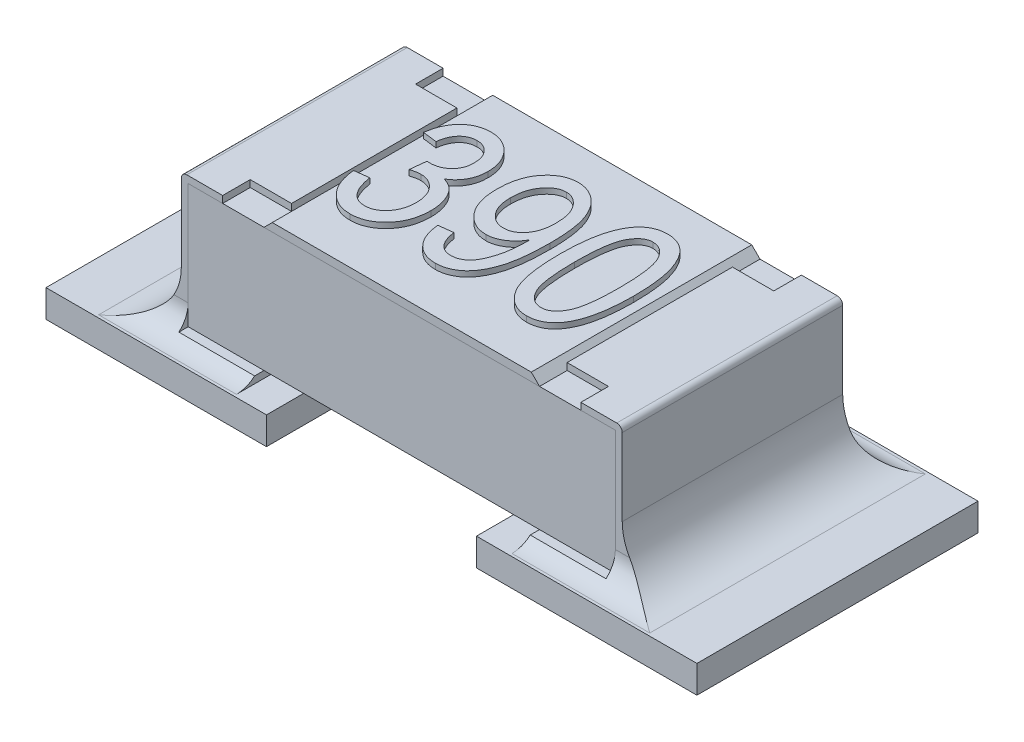
SolidWorks part; units mm, degrees
material "Ceramic Porcelain"
ref_plane "Front Plane" through (0, 0, 0) normal (0, 0, 1) x (1, 0, 0)
ref_plane "Top Plane" through (0, 0, 0) normal (0, 1, 0) x (1, 0, 0)
ref_plane "Right Plane" through (0, 0, 0) normal (1, 0, 0) x (0, 0, -1)
sketch "Sketch1" plane through (0, 0, 0) normal (1, 0, 0) x (0, 0, -1)
  line L0 (0, 55) -> (0, -55) construction
  line L1 (-0.4, 0.575) -> (0.4, 0.575)
  line L2 (-0.4, 0.575) -> (-0.4, 0.125)
  line L3 (-0.4, 0.125) -> (0.4, 0.125)
  line L4 (0.4, 0.575) -> (0.4, 0.125)
  line L5 (55, 0) -> (-55, 0) construction
  dimension "D1" = 0.8
  dimension "D2" = 0.4
  dimension "D3" = 0.45
  dimension "D4" = 0.125
extrude "Boss-Extrude1" add sketch "Sketch1" along normal mid plane 1.55
sketch "Sketch2" plane through (0, 0, 0) normal (0, 0, 1) x (1, 0, 0)
  line L0 (-0.5, 0.6) -> (-0.78, 0.6)
  line L1 (-0.8, 0.58) -> (-0.8, 0.1)
  line L2 (-0.8, 0.1) -> (-0.5, 0.1)
  line L3 (-0.5, 0.1) -> (-0.5, 0.125)
  line L4 (0.775, 0.125) -> (-0.775, 0.125) construction
  line L5 (-0.5, 0.125) -> (-0.775, 0.125)
  line L6 (-0.775, 0.125) -> (-0.775, 0.575)
  line L7 (-0.775, 0.575) -> (-0.5, 0.575)
  line L8 (0.775, 0.575) -> (-0.775, 0.575) construction
  line L9 (-0.5, 0.575) -> (-0.5, 0.6)
  line L11 (0.5, 0.575) -> (0.5, 0.6)
  line L12 (0.5, 0.6) -> (0.78, 0.6)
  line L13 (0.8, 0.58) -> (0.8, 0.1)
  line L14 (0.8, 0.1) -> (0.5, 0.1)
  line L15 (0.5, 0.1) -> (0.5, 0.125)
  line L16 (0.5, 0.125) -> (0.775, 0.125)
  line L17 (0.775, 0.125) -> (0.775, 0.575)
  line L18 (0.775, 0.575) -> (0.5, 0.575)
  arc A0 (0.78, 0.6) -> (0.8, 0.58) centre (0.78, 0.58) cw
  arc A1 (-0.78, 0.6) -> (-0.8, 0.58) centre (-0.78, 0.58) ccw
  point P28 (-0.8, 0.6)
  dimension "D6" = 0.02
  dimension "D1" = 0.025
  dimension "D2" = 0.025
  dimension "D3" = 0.025
  dimension "D4" = 0.3
  dimension "D5" = 0.3
extrude "Boss-Extrude2" add sketch "Sketch2" along normal mid plane 0.8 separate body
sketch "Sketch3" plane through (0, 0.6, 0) normal (0, 1, 0) x (1, 0, 0)
  line L0 (0.5, -0.4) -> (0.5, 0.4) construction
  line L1 (-0.5, 0.4) -> (-0.65, 0.4)
  line L2 (-0.5, 0.4) -> (-0.5, 0.3)
  line L3 (-0.5, 0.3) -> (-0.65, 0.3)
  line L4 (-0.65, 0.4) -> (-0.65, 0.3)
  line L5 (-0.5, -0.4) -> (-0.65, -0.4)
  line L6 (-0.5, -0.4) -> (-0.5, -0.3)
  line L7 (-0.5, -0.3) -> (-0.65, -0.3)
  line L8 (-0.65, -0.4) -> (-0.65, -0.3)
  line L9 (0.5, -0.4) -> (0.65, -0.4)
  line L10 (0.5, -0.4) -> (0.5, -0.3)
  line L11 (0.5, -0.3) -> (0.65, -0.3)
  line L12 (0.65, -0.4) -> (0.65, -0.3)
  line L13 (0.775, -0.4) -> (-0.775, -0.4) construction
  line L15 (0.5, 0.4) -> (0.65, 0.4)
  line L16 (0.5, 0.4) -> (0.5, 0.3)
  line L17 (0.5, 0.3) -> (0.65, 0.3)
  line L18 (0.65, 0.4) -> (0.65, 0.3)
  dimension "D1" = 0.15
  dimension "D2" = 0.1
extrude "Cut-Extrude1" cut sketch "Sketch3" against normal blind 0.025
sketch "Sketch4" plane through (0, 0, 0) normal (0, 0, 1) x (1, 0, 0)
  line L0 (-0.5, 0.575) -> (0.5, 0.575)
  line L1 (0.5, 0.575) -> (0.47, 0.605)
  line L2 (0.47, 0.605) -> (-0.47, 0.605)
  line L3 (-0.47, 0.605) -> (-0.5, 0.575)
  dimension "D1" = 45
  dimension "D2" = 45
  dimension "D3" = 0.03
extrude "Boss-Extrude3" add sketch "Sketch4" along normal mid plane 0.8 separate body
sketch "Sketch7" plane through (0, 0, 0) normal (0, 1, 0) x (1, 0, 0)
  line L0 (0, -0.2833) -> (0, 0.2833) construction
  line L1 (-0.381, -0.51) -> (-1.181, -0.51)
  line L2 (-0.381, -0.51) -> (-0.381, 0.51)
  line L3 (-0.381, 0.51) -> (-1.181, 0.51)
  line L4 (-1.181, -0.51) -> (-1.181, 0.51)
  line L5 (0.381, -0.51) -> (1.181, -0.51)
  line L6 (0.381, -0.51) -> (0.381, 0.51)
  line L7 (0.381, 0.51) -> (1.181, 0.51)
  line L8 (1.181, -0.51) -> (1.181, 0.51)
  line L9 (-0.2833, 0) -> (0.2833, 0) construction
  dimension "D1" = 0.8
  dimension "D2" = 0.381
  dimension "D3" = 0.381
  dimension "D4" = 1.02
  dimension "D5" = 0.51
extrude "Boss-Extrude5" add sketch "Sketch7" along normal blind 0.1
fillet "Fillet3" radius 0.2 1 edges at (-0.8, 0.1, 0)
fillet "Fillet4" radius 0.2 1 edges at (0.8, 0.1, 0)
fillet "Fillet5" radius 0.1 2 edges at (0.75, 0.1, -0.4) (0.75, 0.1, 0.4)
fillet "Fillet6" radius 0.1 2 edges at (-0.75, 0.1, 0.4) (-0.75, 0.1, -0.4)
sketch "Esquisse2" plane through (0, 0.605, 0) normal (0, 1, 0) x (1, 0, 0)
  text T0 "390" font "Arial Narrow" height 0.5
extrude "Boss.-Extru.1" add sketch "Esquisse2" along normal blind 0.02
